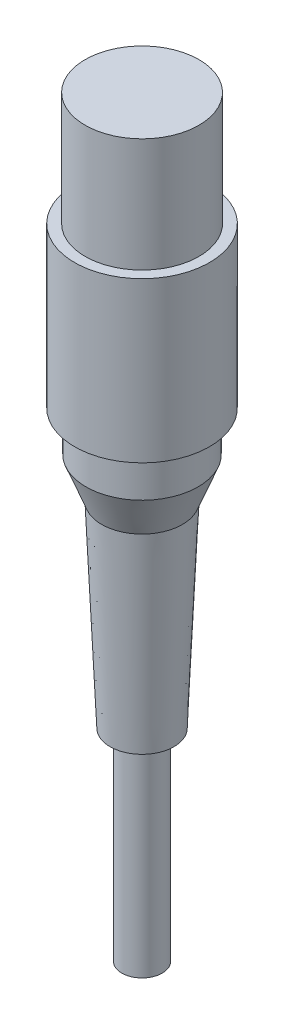
SolidWorks part; units mm, degrees
ref_plane "Front Plane" through (0, 0, 0) normal (0, 0, 1) x (1, 0, 0)
ref_plane "Top Plane" through (0, 0, 0) normal (0, 1, 0) x (1, 0, 0)
ref_plane "Right Plane" through (0, 0, 0) normal (1, 0, 0) x (0, 0, -1)
sketch "Sketch1" plane through (0, 0, 0) normal (0, 0, 1) x (1, 0, 0)
  line L0 (0, 0) -> (0, 81.78)
  line L1 (0, 81.78) -> (8.45, 81.78)
  line L2 (8.45, 81.78) -> (8.45, 64.9)
  line L3 (8.45, 64.9) -> (10.015, 64.9)
  line L4 (10.015, 64.9) -> (10.015, 41.21)
  line L5 (10.015, 41.21) -> (8.33, 41.21)
  line L6 (8.33, 41.21) -> (8.33, 35.21)
  line L7 (8.33, 35.21) -> (6, 29.21)
  line L8 (6, 29.21) -> (4.75, 0)
  line L9 (4.75, 0) -> (0, 0)
  line L10 (0, 0) -> (0, 117.5182) construction
  line L11 (10.015, 41.21) -> (0, 41.21)
  dimension "D1" = 16.88
  dimension "D2" = 23.69
  dimension "D3" = 6
  dimension "D4" = 6
  dimension "D5" = 41.21
  dimension "D6" = 16.9
  dimension "D7" = 20.03
  dimension "D8" = 16.66
  dimension "D9" = 12
  dimension "D10" = 9.5
revolve "Revolve1" add sketch "Sketch1" angle 360 about L10 region at (4.7137, 60.6713, 0)
revolve "Revolve2" add sketch "Sketch1<3>" angle 360 about L10 region at (3.1499, 22.7358, 0)
sketch "Sketch1<3>" plane through (0, 0, 0) normal (0, 0, 1) x (1, 0, 0) same geometry as "Sketch1"
sketch "Sketch2" plane through (0, 0, 0) normal (0, -1, 0) x (1, 0, 0)
  circle A0 centre (0, 0) radius 3
  dimension "D1" = 6
extrude "Boss-Extrude1" add sketch "Sketch2" along normal blind 30
